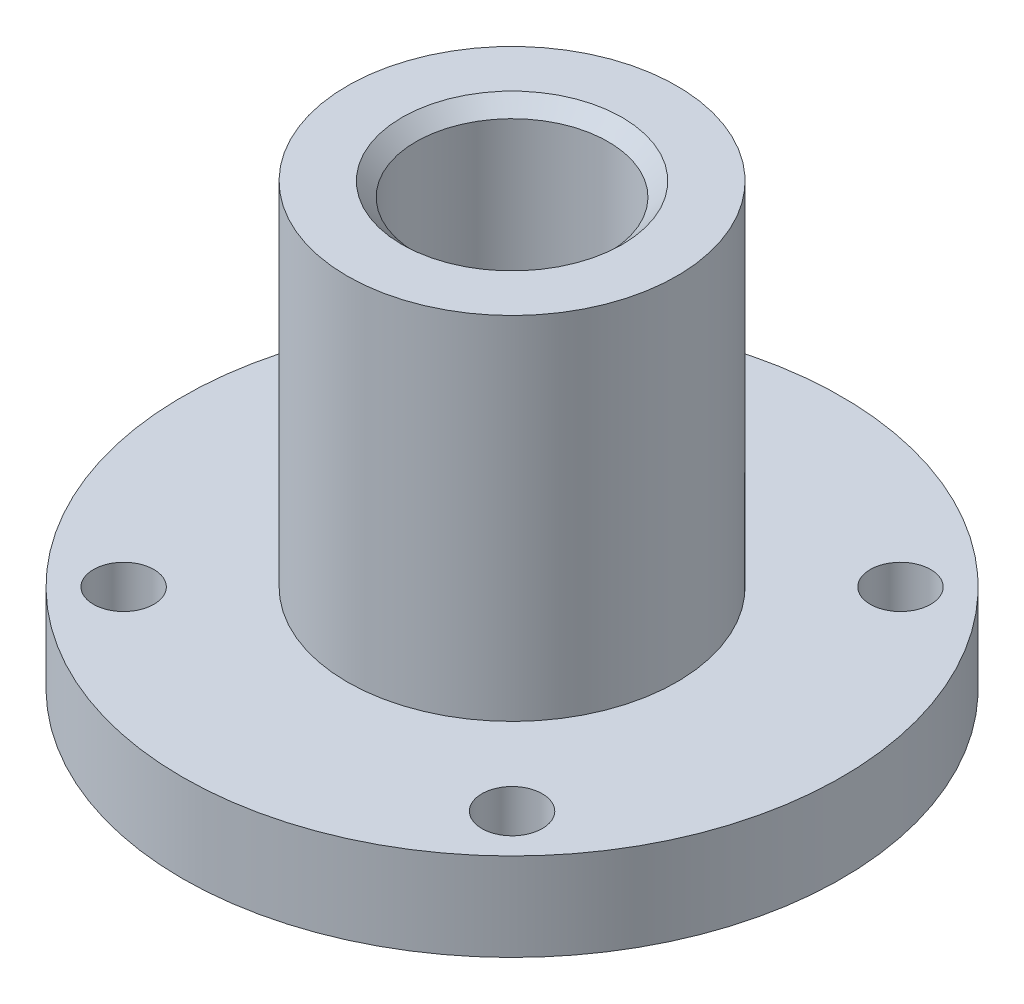
SolidWorks part; units mm, degrees
material "БрАЖ9-4 ГОСТ 18175-78"
ref_plane "Спереди" through (0, 0, 0) normal (0, 0, 1) x (1, 0, 0)
ref_plane "Сверху" through (0, 0, 0) normal (0, 1, 0) x (1, 0, 0)
ref_plane "Справа" through (0, 0, 0) normal (1, 0, 0) x (0, 0, -1)
ref_axis "ОсьX" through (-88.99, 0, 0) along (1, 0, 0)
ref_axis "ОсьZ" through (0, 55, 0) along (0, -1, 0)
ref_axis "ОсьY" through (0, 0, -88.99) along (0, 0, 1)
sketch "Эскиз1" plane through (0, 0, 0) normal (0, 0, 1) x (1, 0, 0)
  line L0 (0, 20.9835) -> (0, -14.3325) construction
  line L1 (0, 0) -> (-30, 0)
  line L2 (-30, 0) -> (-30, 8)
  line L3 (-30, 8) -> (-15, 8)
  line L4 (-15, 8) -> (-15, 40)
  line L5 (-15, 40) -> (0, 40)
  line L6 (0, 40) -> (0, 0)
  dimension "D1" = 30
  dimension "D2" = 60
  dimension "D3" = 8
  dimension "D4" = 40
revolve "Повернуть1" add sketch "Эскиз1" angle 360 mid plane about L0
hole_wizard "Отверстие обработанное метчиком M201" positions "Эскиз2" profile "Эскиз3" tap size "M20" standard "GOST" end condition through all
sketch "Эскиз2" plane through (0, 40, 0) normal (0, 1, 0) x (1, 0, 0)
  point P0 (0, 0)
sketch "Эскиз3" plane through (0, 40, 0) normal (1, 0, 0) x (0, 0, 1)
  line L0 (0, 0) -> (0, 40)
  line L1 (0, 40) -> (8.75, 40)
  line L2 (8.75, 40) -> (8.75, 1.275)
  line L3 (8.75, 1.275) -> (10.025, 0)
  line L5 (10.025, 0) -> (0, 0)
  line L6 (-8.75, 1.275) -> (-10.025, 0) construction
  line L11 (0, -6.35) -> (0, 107.95) construction
  dimension "Диаметр проходного сверла" = 17.5
  dimension "Глубина проходного сверла" = 40
  dimension "Диаметр передней зенковки" = 20.05
  dimension "Угол передней зенковки" = 90
cosmetic thread "Отверстие резьбы1"
sketch "Эскиз4" plane through (0, 8, 0) normal (0, 1, 0) x (1, 0, 0)
  line L0 (-17.6777, 17.6777) -> (0, 0) construction
  line L1 (0, 0) -> (0, 25) construction
  circle A0 centre (-17.6777, 17.6777) radius 2.75
  circle A1 centre (-17.6777, -17.6777) radius 2.75
  circle A2 centre (17.6777, 17.6777) radius 2.75
  circle A3 centre (17.6777, -17.6777) radius 2.75
  circle A4 centre (0, 0) radius 25 construction
  dimension "D2" = 5.5
  dimension "D3" = 50
  dimension "D1" = 45
extrude "Вырез-Вытянуть1" cut sketch "Эскиз4" against normal through all
